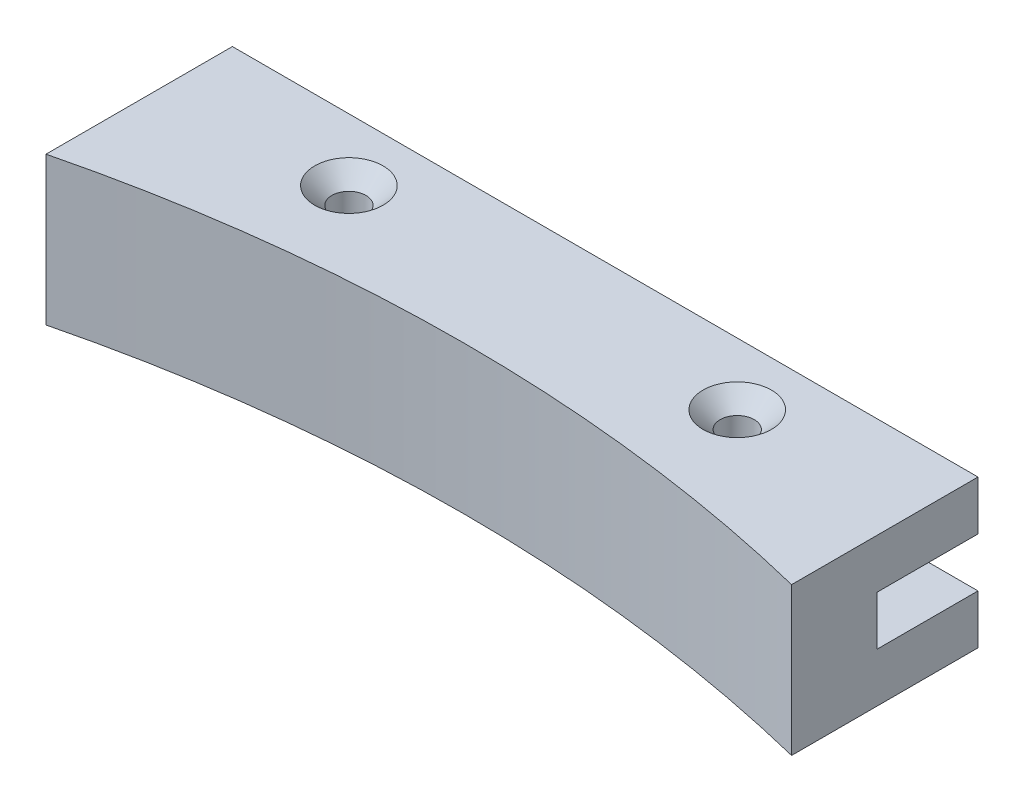
SolidWorks part; units mm, degrees
material "6061-T6 (SS)"
ref_plane "Front Plane" through (0, 0, 0) normal (0, 0, 1) x (1, 0, 0)
ref_plane "Top Plane" through (0, 0, 0) normal (0, 1, 0) x (1, 0, 0)
ref_plane "Right Plane" through (0, 0, 0) normal (1, 0, 0) x (0, 0, -1)
sketch "Sketch1" plane through (0, 0, 0) normal (0, 1, 0) x (1, 0, 0)
  line L0 (-24, 0) -> (24, 0)
  line L1 (24, 0) -> (24, -12)
  line L2 (-24, 0) -> (-24, -12)
  line L3 (-24, -9.0773) -> (24, -9.0773) construction
  line L25 (-24, -12) -> (0, -109.0773) construction
  line L26 (0, -109.0773) -> (24, -12) construction
  arc A0 (-24, -12) -> (24, -12) centre (0, -109.0773) cw
  point P0 (0, 0)
  dimension "D1" = 12
  dimension "D2" = 100
  dimension "D5" = 48
extrude "Boss-Extrude1" add sketch "Sketch1" along normal mid plane 9.525
hole_wizard "CSK for M2 Flat Head Machine Screw1" positions "Sketch10" profile "Sketch11" countersink size "M2" standard "ANSI Metric" end condition through all
sketch "Sketch10" plane through (0, 4.7625, 0) normal (0, 1, 0) x (1, 0, 0)
  line L0 (0, -0.121) -> (0, -16.3024) construction
  line L1 (24, 0) -> (-24, 0) construction
  point P8 (-12.5, -4)
  point P13 (12.5, -4)
  dimension "D1" = 12.5
  dimension "D2" = 4
sketch "Sketch11" plane through (12.5, 4.7625, 4) normal (1, 0, 0) x (0, 0, 1)
  line L0 (0, 0) -> (0, 9.525)
  line L1 (0, 9.525) -> (1.1, 9.525)
  line L2 (1.1, 9.525) -> (1.1, 1.1)
  line L3 (1.1, 1.1) -> (2.2, 0)
  line L5 (2.2, 0) -> (0, 0)
  line L6 (-1.1, 1.1) -> (-2.2, 0) construction
  line L11 (0, -6.35) -> (0, 107.95) construction
  dimension "Thru Hole Dia." = 2.2
  dimension "Thru Hole Depth" = 9.525
  dimension "Near C'Sink Dia." = 4.4
  dimension "Near C'Sink Angle" = 90
sketch "Sketch9" plane through (-24, 0, 0) normal (-1, 0, 0) x (0, 0, 1)
  line L0 (0, 4.7625) -> (0, -4.7625) construction
  line L1 (0, -1.5875) -> (6.5, -1.5875)
  line L2 (0, -1.5875) -> (0, 1.5875)
  line L3 (0, 1.5875) -> (6.5, 1.5875)
  line L4 (6.5, -1.5875) -> (6.5, 1.5875)
  point P6 (0, 0)
  dimension "D1" = 3.175
  dimension "D2" = 6.5
extrude "Cut-Extrude2" cut sketch "Sketch9" against normal through all
